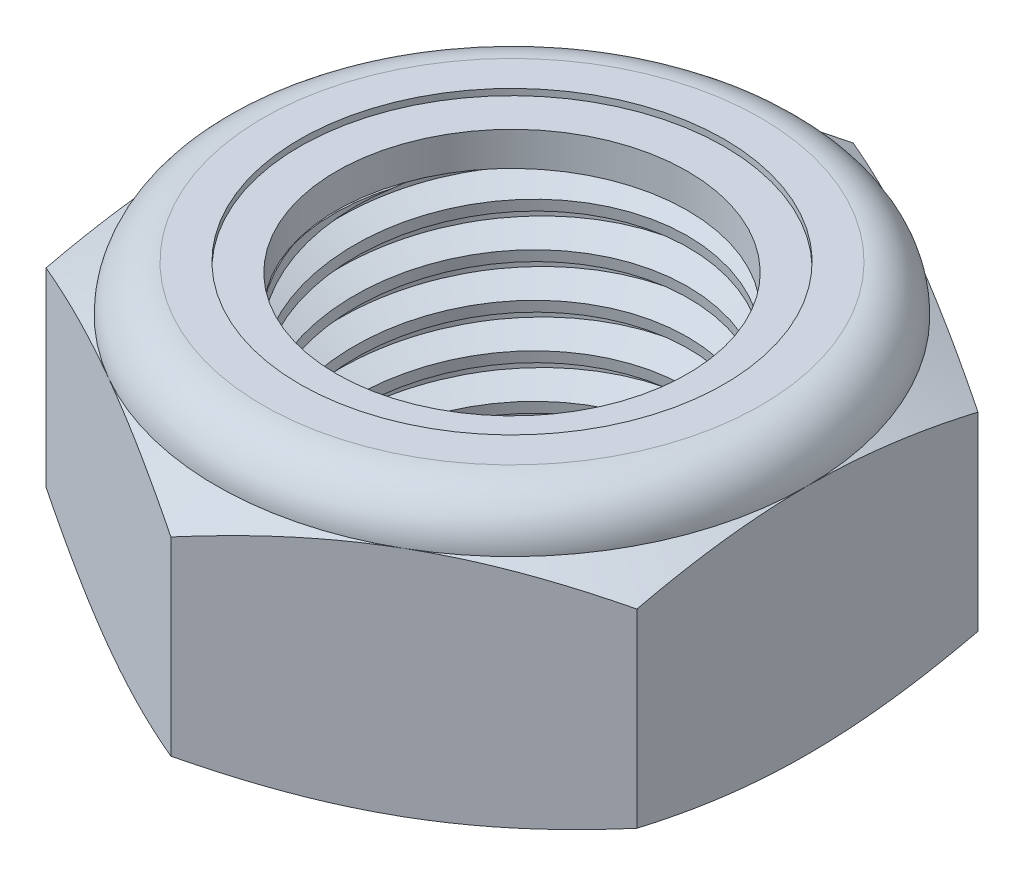
SolidWorks part; units mm, degrees
ref_plane "Front" through (0, 0, 0) normal (0, 0, 1) x (1, 0, 0)
ref_plane "Top" through (0, 0, 0) normal (0, 1, 0) x (1, 0, 0)
ref_plane "Right" through (0, 0, 0) normal (1, 0, 0) x (0, 0, -1)
sketch "Sketch1" plane through (0, 0, 0) normal (0, 1, 0) x (1, 0, 0)
  line L1 (0, 8.2489) -> (-7.1438, 4.1244)
  line L2 (-7.1438, 4.1244) -> (-7.1438, -4.1244)
  line L3 (-7.1438, -4.1244) -> (0, -8.2489)
  line L4 (0, -8.2489) -> (7.1438, -4.1244)
  line L5 (7.1438, -4.1244) -> (7.1437, 4.1244)
  line L6 (7.1437, 4.1244) -> (0, 8.2489)
  circle A0 centre (0, 0) radius 7.1438 construction
  dimension "Hex Flats" = 14.2875
extrude "Extrude1" add sketch "Sketch1" along normal blind 6.7469
sketch "Sketch2" plane through (0, 0, 0) normal (1, 0, 0) x (0, 0, -1)
  line L0 (-4.7625, 0) -> (-4.7625, 6.7469) construction
  line L1 (0, 0) -> (4.7625, 0)
  line L2 (0, 0) -> (0, 6.7469)
  line L3 (0, 6.7469) -> (4.7625, 6.7469)
  line L4 (4.7625, 0) -> (4.7625, 6.7469)
  line L5 (-4.1244, 6.7469) -> (4.1244, 6.7469) construction
  line L7 (0, -4.7625) -> (0, 0) construction
  dimension "Thread Dia" = 9.525
revolve "Revolve1" add sketch "Sketch2" angle 360 about L7
sketch "Sketch3" plane through (0, 0, 0) normal (1, 0, 0) x (0, 0, -1)
  line L0 (4.7625, 6.7469) -> (-4.7625, 6.7469) construction
  line L1 (-4.7625, 6.7469) -> (-4.7625, 5.6885) construction
  line L2 (-4.7625, 5.6885) -> (4.7625, 6.7469) construction
  line L3 (4.7625, 6.7469) -> (4.7771, 6.6154) construction
  line L4 (4.7771, 6.6154) -> (4.8794, 5.695)
  line L5 (4.8794, 5.695) -> (4.2735, 5.9605)
  line L6 (4.2735, 5.9605) -> (4.2443, 6.2234)
  line L7 (4.2443, 6.2234) -> (4.7771, 6.6154)
  line L8 (4.2589, 6.0919) -> (4.8282, 6.1552) construction
  line L9 (4.7625, 6.7469) -> (4.7625, 6.1479) construction
  line L10 (4.7625, 6.1479) -> (-4.7625, 5.0896) construction
  line L11 (-4.7625, 5.0896) -> (-4.7625, 5.6885) construction
  line L12 (-0.1253, 6.7469) -> (0.1253, 4.4906) construction
  line L13 (-4.7625, 0) -> (-4.7625, 6.7469) construction
  line L14 (0, 6.7469) -> (4.7625, 6.7469) construction
  line L15 (4.7625, 0) -> (4.7625, 6.7469) construction
  point P13 (0, 5.6187)
  dimension "D1" = 0.1323
  dimension "D2" = 0.2646
  dimension "Thread Pitch" = 1.0583
  dimension "D4" = 60
  dimension "D5" = 1.0583
revolve "Cut-Revolve1" cut sketch "Sketch3" angle 360 about L12
pattern_linear "LPattern1" count 6 spacing 1.0583 along (0, -1, 0) count 2 spacing 1.0583 along (0, 1, 0) of "Cut-Revolve1"
sketch "Sketch4" plane through (0, 0, 0) normal (1, 0, 0) x (0, 0, -1)
  line L0 (0, 6.7469) -> (4.7625, 6.7469)
  line L1 (4.7625, 6.7469) -> (4.2443, 6.5052)
  line L2 (4.2443, 6.5052) -> (4.2443, 0.2416)
  line L3 (4.2443, 0.2416) -> (4.7625, 0)
  line L4 (4.7625, 0) -> (0, 0)
  line L5 (0, 0) -> (0, 6.7469)
  line L6 (4.7625, 0) -> (4.7625, 6.7469) construction
  line L7 (0, 6.7469) -> (4.7625, 6.7469) construction
  line L8 (0, 0) -> (4.7625, 0) construction
  line L9 (0, 0) -> (0, 6.7469) construction
  line L10 (0, 6.7469) -> (0, 7.3186) construction
  dimension "D1" = 25
revolve "Cut-Revolve2" cut sketch "Sketch4" angle 360 about L10
combine bodies "Combine1" operation type subtract main body 112 bodies to subtract 111
sketch "Sketch5" plane through (0, 0, 0) normal (1, 0, 0) x (0, 0, -1)
  line L0 (0, 0) -> (7.1438, 0)
  line L1 (7.1438, 0) -> (8.2489, 0.5153)
  line L2 (8.2489, 0.5153) -> (8.2489, 5.1071)
  line L3 (8.2489, 5.1071) -> (7.1438, 5.6224)
  line L4 (6.0193, 6.7469) -> (6.0193, 8.0169)
  line L5 (6.0193, 8.0169) -> (9.5189, 8.0169)
  line L6 (9.5189, 8.0169) -> (9.5189, -1.27)
  line L7 (9.5189, -1.27) -> (0, -1.27)
  line L8 (0, -1.27) -> (0, 0)
  line L9 (7.1438, 5.6224) -> (7.1438, 0) construction
  line L10 (0, 0) -> (4.7625, 0) construction
  line L13 (8.2489, 2.8112) -> (9.5189, 2.8112) construction
  line L14 (8.2489, 6.7469) -> (8.2489, 0) construction
  line L15 (0, 0) -> (0, 8.0169) construction
  line L20 (0, 8.0169) -> (6.0193, 8.0169) construction
  line L22 (0, 6.7469) -> (4.7625, 6.7469) construction
  arc A0 (7.1438, 5.6224) -> (6.0193, 6.7469) centre (6.0193, 5.6224) ccw
  dimension "D1" = 25
  dimension "D2" = 1.27
  dimension "D3" = 6.7469
  dimension "D4" = 1.1245
revolve "Cut-Revolve3" cut sketch "Sketch5" angle 360 about L15
sketch "Sketch6" plane through (0, 0, 0) normal (1, 0, 0) x (0, 0, -1)
  line L0 (0, 5.6224) -> (6.9914, 5.6224)
  line L1 (6.0193, 6.5945) -> (5.1318, 6.5945)
  line L2 (0, 8.0169) -> (0, 5.6224)
  line L3 (5.1318, 8.0169) -> (0, 8.0169)
  line L4 (0, 8.0169) -> (6.0193, 8.0169) construction
  line L5 (0, 0) -> (0, 8.0169) construction
  line L6 (0, 8.0169) -> (0, 44.323) construction
  line L7 (5.1318, 6.5945) -> (5.1318, 8.0169)
  line L8 (6.0193, 6.7469) -> (6.0193, 6.5945) construction
  line L9 (5.1318, 6.5945) -> (4.2443, 6.5945) construction
  line L10 (4.2443, 6.5945) -> (4.2443, 6.5052) construction
  arc A0 (6.9914, 5.6224) -> (6.0193, 6.5945) centre (6.0193, 5.6224) ccw
  arc A1 (7.1438, 5.6224) -> (6.0193, 6.7469) centre (6.0193, 5.6224) ccw construction
  dimension "D1" = 0.1524
revolve "Cut-Revolve4" cut sketch "Sketch6" angle 360 about L6
sketch "Sketch7" plane through (0, 0, 0) normal (1, 0, 0) x (0, 0, -1)
  line L0 (4.2443, 5.6986) -> (6.9119, 5.6986)
  line L1 (6.0193, 6.5183) -> (4.2443, 6.5183)
  line L2 (4.2443, 6.5183) -> (4.2443, 5.6986)
  line L3 (4.2443, 5.6986) -> (0, 5.6986) construction
  line L4 (0, 5.6986) -> (0, 6.5183) construction
  line L5 (0, 6.5183) -> (4.2443, 6.5183) construction
  line L6 (4.2443, 5.6986) -> (4.2443, 5.6224) construction
  line L7 (0, 5.6224) -> (6.9914, 5.6224) construction
  line L8 (6.0193, 6.5183) -> (6.0193, 6.5945) construction
  arc A0 (6.9119, 5.6986) -> (6.0193, 6.5183) centre (6.0193, 5.6224) ccw
  arc A2 (6.9914, 5.6224) -> (6.0193, 6.5945) centre (6.0193, 5.6224) ccw construction
  dimension "D1" = 0.0762
revolve "Revolve2" add sketch "Sketch7" angle 360 about L4
equation "\"D1@Sketch3\"=\"Thread Pitch@Sketch3\"/8"
equation "\"D2@Sketch3\"=\"Thread Pitch@Sketch3\"/4"
equation "\"D5@Sketch3\"=\"Thread Pitch@Sketch3\""
equation "\"D4@LPattern1\"=\"Thread Pitch@Sketch3\""
equation "\"D3@LPattern1\"=\"Thread Pitch@Sketch3\""
equation "\"D1@LPattern1\"=\"Height@Extrude1\"/\"Thread Pitch@Sketch3\""
equation "\"D4@Sketch5\"=\"Height@Extrude1\"/6"
